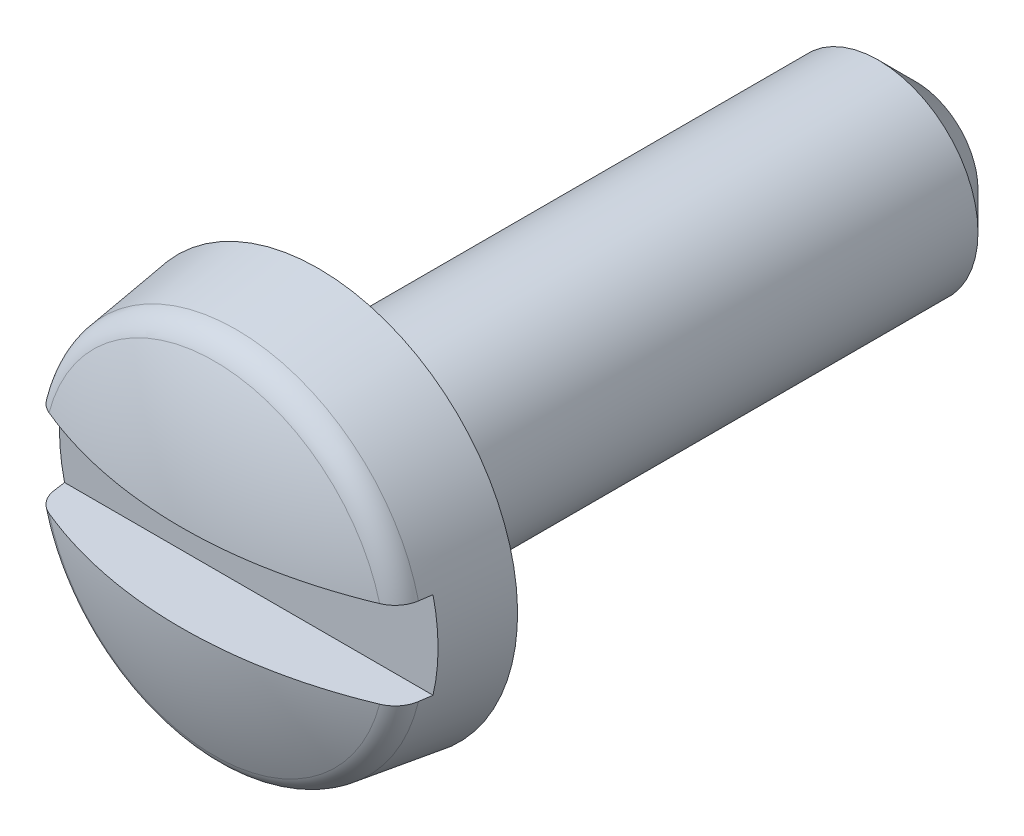
SolidWorks part; units mm, degrees
material "AISI 304"
ref_plane "Front" through (0, 0, 0) normal (0, 0, 1) x (1, 0, 0)
ref_plane "Top" through (0, 0, 0) normal (0, 1, 0) x (1, 0, 0)
ref_plane "Right" through (0, 0, 0) normal (1, 0, 0) x (0, 0, -1)
sketch "Sketch1" plane through (0, 0, 0) normal (0, 0, 1) x (1, 0, 0)
  circle A0 centre (0, 0) radius 1
  dimension "Head Dia" = 2
extrude "Extrude3" add sketch "Sketch1" along normal blind 0.7
sketch "Sketch11" plane through (0, 0, 0) normal (1, 0, 0) x (0, 0, -1)
  line L0 (0, 0) -> (-0.954, 0) construction
  line L4 (-0.7, 1) -> (-0.7, -1) construction
  line L5 (-0.954, 1.04) -> (0, 1.04)
  line L7 (0, 1.04) -> (0, 1)
  line L8 (-0.4138, 0.9418) -> (0, 1)
  line L9 (0, -1) -> (0, 1) construction
  line L13 (-0.7, 0) -> (-0.954, 0)
  line L14 (-0.954, 0) -> (-0.954, 1.04)
  arc A0 (-0.5228, 0.8586) -> (-0.7, 0) centre (1.4693, 0) ccw
  arc A1 (-0.4138, 0.9418) -> (-0.5228, 0.8586) centre (-0.3943, 0.8032) ccw
  point P13 (-0.49, 0.9311)
  dimension "D1" = 0.14
  dimension "D3" = 0.254
  dimension "D5" = 0.04
  dimension "D2" = 0.21
  dimension "D4" = 8
revolve "Cut-Revolve3" cut sketch "Sketch11" angle 360 about L0
sketch "Sketch4" plane through (0, 0, 0) normal (1, 0, 0) x (0, 0, -1)
  line L0 (0, 0) -> (3, 0)
  line L3 (3, 0) -> (3, 0.5)
  line L4 (3, 0.5) -> (0, 0.5)
  line L6 (0, 0.5) -> (0, 0)
  line L9 (3, 0.5) -> (3, -0.5) construction
  dimension "length" = 3
  dimension "dia" = 1
revolve "Revolve1" add sketch "Sketch4" angle 360 about L0
sketch "Sketch13" plane through (0, 0, -3) normal (0, 0, -1) x (-1, 0, 0)
  circle A2 centre (0, 0) radius 0.5
curve "Helix/Spiral1" [suppressed] pitch 0.25 height 3 turns 12
chamfer "Chamfer2" distance 0.1875 angle 45 1 edges at (0.5, 0, -3)
sketch "Sketch14" plane through (0, 0, 0) normal (1, 0, 0) x (0, 0, -1)
  line L0 (3, 0.5156) -> (3.2188, 0.5156)
  line L1 (3.2188, 0.5156) -> (3.125, 0.3465)
  line L2 (3.125, 0.3465) -> (3.0938, 0.3465)
  line L3 (3.0938, 0.3465) -> (3, 0.5156)
  line L4 (3.0469, 0.4311) -> (3.1719, 0.4311) construction
  line L5 (3, 0.5) -> (0, 0.5) construction
  dimension "D1" = 0.0312
  dimension "D2" = 58
  dimension "D3" = 0.125
  dimension "D4" = 0.0156
sweep "Cut-Sweep1" [suppressed] cut profiles "Sketch14" path "Helix/Spiral1"
ref_plane "Plane1" through (0, 0, 35.1) normal (0, 0, -1) x (-1, 0, 0)
sketch "Sketch29" [suppressed] plane through (0, 0, 28.575) normal (0, 0, -1) x (-1, 0, 0)
  circle A0 centre (0, 0) radius 1.7526 construction
  circle A1 centre (0, 0) radius 1.7526
  point P3 (0, -1.7526)
  point P4 (0, 1.7526)
extrude "Extrude11" [suppressed] add sketch "Sketch29" against normal up to surface (28.575 mm away)
ref_plane "Plane2" through (0, 0, 0.7) normal (0, 0, 1) x (1, 0, 0)
sketch "Sketch32" plane through (0, 0, 0.7) normal (0, 0, 1) x (1, 0, 0)
  line L0 (-1, 0.2187) -> (1, -0.2187) construction
  line L1 (-1, 0.2187) -> (1, 0.2187)
  line L2 (-1, 0.2187) -> (-1, -0.2188)
  line L3 (-1, -0.2188) -> (1, -0.2187)
  line L4 (1, 0.2187) -> (1, -0.2187)
  circle A0 centre (0, 0) radius 1 construction
  dimension "D1" = 0.4375
extrude "Extrude16" cut sketch "Sketch32" against normal blind 0.35
sketch "Sketch18" plane through (0, 0, 0) normal (1, 0, 0) x (0, 0, -1)
  line L1 (3, 0.5) -> (0, 0.5) construction
  point P0 (2.625, -0.5)
  point P1 (2.75, 0.5)
  point P2 (-0.7, 0.2187)
  dimension "D1" = 0.25
  dimension "D2" = 0.375
other "DeleteFace1" [suppressed]
equation "\"D3@Helix/Spiral1\" = \"length@Sketch4\""
equation "\"D1@Sketch14\" = \"D4@Helix/Spiral1\" * .125"
equation "\"D3@Sketch14\" = \"D4@Helix/Spiral1\" * .5"
equation "\"D5@Sketch11\" = \"Head Dia@Sketch1\" * .02"
equation "\"D1@Chamfer2\" = \"D4@Helix/Spiral1\" * .75"
equation "\"D1@Sketch18\" = \"D4@Helix/Spiral1\""
equation "\"D2@Sketch18\" = \"D4@Helix/Spiral1\" * 1.5"
equation "\"D2@Sketch11\" = \"Head Ht@Extrude3\" * .3"
equation "\"D1@Extrude16\" = \"Head Ht@Extrude3\" * .5"
equation "\"D1@Sketch11\" = \"Head Ht@Extrude3\" * .2"
equation "\"D4@Sketch14\" = \"D1@Sketch14\" * .5"
equation "\"D1@Sketch32\" = \"D4@Helix/Spiral1\" * 1.75"
